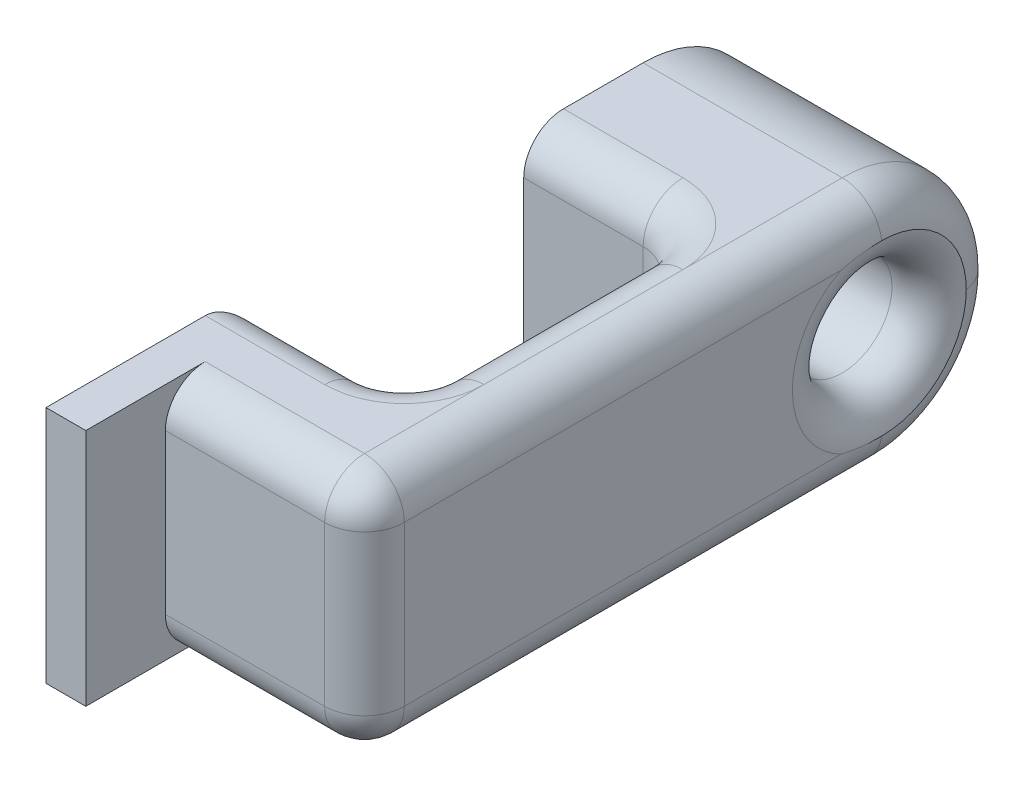
SolidWorks part; units mm, degrees
ref_plane "Спереди" through (0, 0, 0) normal (0, 0, 1) x (1, 0, 0)
ref_plane "Сверху" through (0, 0, 0) normal (0, 1, 0) x (1, 0, 0)
ref_plane "Справа" through (0, 0, 0) normal (1, 0, 0) x (0, 0, -1)
sketch "Эскиз1" plane through (0, 0, 0) normal (0, 1, 0) x (1, 0, 0)
  line L0 (0, 0) -> (0, 5)
  line L1 (0, 5) -> (4, 5)
  line L2 (4, 5) -> (4, 12)
  line L3 (4, 12) -> (0, 12)
  line L4 (0, 12) -> (0, 18)
  line L5 (0, 18) -> (6, 18)
  line L6 (6, 18) -> (6, 2)
  line L7 (6, 2) -> (1, 2)
  line L8 (1, 2) -> (1, 0)
  line L9 (1, 0) -> (0, 0)
  dimension "D1" = 1
  dimension "D2" = 4
  dimension "D3" = 2
  dimension "D4" = 3
  dimension "D5" = 7
  dimension "D6" = 6
  dimension "D7" = 2
extrude "Бобышка-Вытянуть1" add sketch "Эскиз1" along normal blind 6
fillet "Скругление1" radius 3 2 edges at (3, 0, -18) (3, 6, -18)
fillet "Скругление2" radius 1 16 edges at (2, 6, -12) (2, 6, -5) (2, 0, -12) (2, 0, -5) (6, 6, -8.5) (6, 5.1213, -17.1213) (6, 0.8787, -17.1213) (0, 3, -5) (4, 6, -8.5) (4, 0, -8.5) (4, 3, -12) (4, 3, -5) (3.5, 6, -2) (3.5, 0, -2) (6, 0, -8.5) (6, 3, -2)
sketch "Эскиз2" plane through (0, 0, 0) normal (-1, 0, 0) x (0, 0, 1)
  circle A0 centre (-15, 3) radius 1.25
  dimension "D1" = 2.5
extrude "Вырез-Вытянуть1" cut sketch "Эскиз2" against normal through all
fillet "Скругление3" radius 1 1 edges at (6, 3, -13.75)
